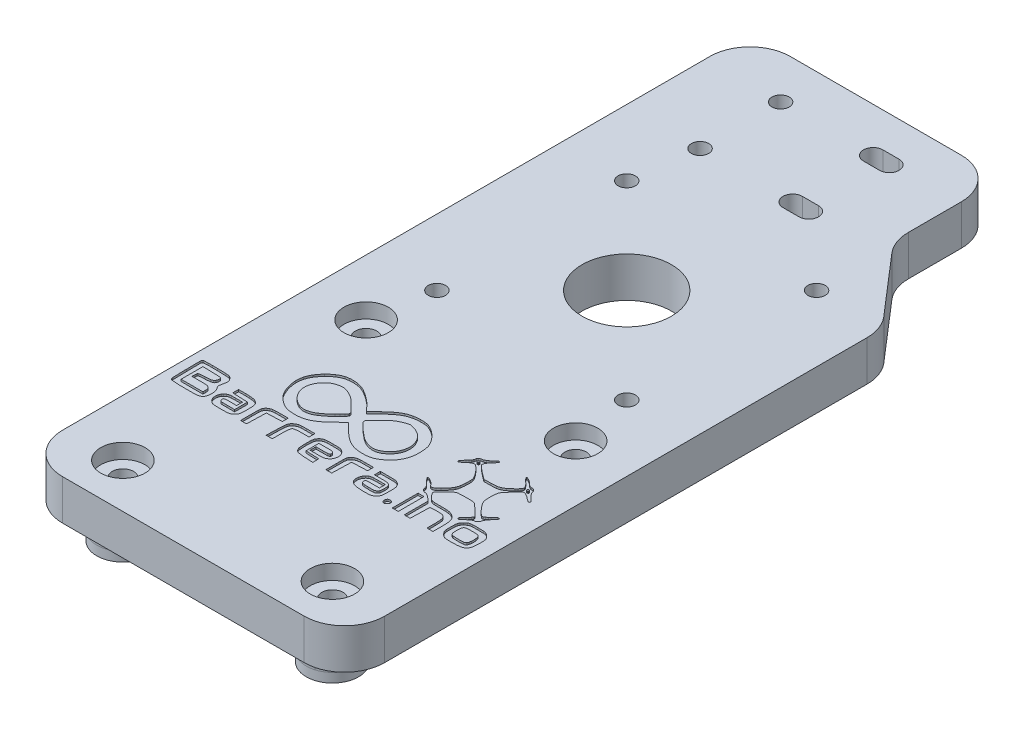
SolidWorks part; units mm, degrees
ref_plane "Alzado" through (0, 0, 0) normal (0, 0, 1) x (1, 0, 0)
ref_plane "Planta" through (0, 0, 0) normal (0, 1, 0) x (1, 0, 0)
ref_plane "Vista lateral" through (0, 0, 0) normal (1, 0, 0) x (0, 0, -1)
sketch "Croquis1" plane through (0, 0, 0) normal (0, 1, 0) x (1, 0, 0)
  line L0 (12.4888, 90.7353) -> (-12.4888, 90.7353)
  line L1 (-12.4888, 90.7353) -> (12.4888, 90.7353)
  line L2 (-40, 39.8326) -> (-40, -80)
  line L3 (-30, -90) -> (30, -90)
  line L4 (40, 39.8326) -> (40, -80)
  line L6 (0, -49) -> (-4.6306, -49) construction
  line L9 (0, 0) -> (0, -51.3503) construction
  line L10 (-12.4888, 90.7353) -> (-30, 90.7353)
  line L11 (24.9172, 61.0325) -> (37.5716, 46.365)
  line L12 (22.4888, 80.7353) -> (22.4888, 67.5648)
  line L13 (-40, 80.7353) -> (-40, 39.8326)
  arc A12 (-40, -80) -> (-30, -90) centre (-30, -80) ccw
  arc A13 (40, -80) -> (30, -90) centre (30, -80) cw
  arc A14 (22.4888, 80.7353) -> (12.4888, 90.7353) centre (12.4888, 80.7353) ccw
  arc A15 (37.5716, 46.365) -> (40, 39.8326) centre (30, 39.8326) cw
  arc A16 (22.4888, 67.5648) -> (24.9172, 61.0325) centre (32.4888, 67.5648) ccw
  arc A17 (-30, 90.7353) -> (-40, 80.7353) centre (-30, 80.7353) ccw
  point P0 (0, 0)
  point P15 (-22.4888, 90.7353)
  point P26 (-40, -90)
  point P29 (40, -90)
  point P40 (22.4888, 90.7353)
  dimension "D1" = 10
  dimension "D3" = 80
extrude "Saliente-Extruir1" add sketch "Croquis1" along normal blind 10 contours L13 L2 L3 L4 L0 region at (-1.4888, 0, 3.0033)
sketch "Croquis2" plane through (0, 0, 0) normal (0, -1, 0) x (1, 0, 0)
  line L0 (-30, 90) -> (30, 90) construction
  line L1 (0, 0) -> (0, 18.1232) construction
  line L2 (-26.0188, 48.8) -> (-13.5394, 48.8) construction
  circle A0 centre (-26.0188, 79) radius 6.5
  circle A1 centre (-26.0188, 79) radius 2.65
  circle A2 centre (-26.0188, 18.6) radius 2.65
  circle A3 centre (-26.0188, 18.6) radius 6.5
  circle A4 centre (26.0188, 79) radius 2.65
  circle A5 centre (26.0188, 79) radius 6.5
  circle A6 centre (26.0188, 18.6) radius 6.5
  circle A7 centre (26.0188, 18.6) radius 2.65
  dimension "D2" = 13
  dimension "D3" = 5.3
  dimension "D1" = 11
  dimension "D4" = 30.2
extrude "Saliente-Extruir2" add sketch "Croquis2" along normal blind 7.3 from surface starting at face at (7.4963, 0, -18.1447)
sketch "Croquis3" plane through (0, 0, 0) normal (0, -1, 0) x (1, 0, 0)
  circle A0 centre (-26.0188, 79) radius 2.65
  circle A1 centre (-26.0188, 18.6) radius 2.65
  circle A2 centre (26.0188, 18.6) radius 2.65
  circle A3 centre (26.0188, 79) radius 2.65
extrude "Cortar-Extruir1" cut sketch "Croquis3" against normal blind 68 and the other way blind 46
sketch "Croquis4" plane through (0, 0, 0) normal (0, -1, 0) x (1, 0, 0)
  line L0 (0, 0) -> (0, -20.1076) construction
  line L1 (0, -20.1076) -> (-7.7372, -20.1076) construction
  circle A0 centre (-23.57, -43.6776) radius 2.15
  circle A1 centre (-23.57, 3.4624) radius 2.15
  circle A2 centre (23.57, 3.4624) radius 2.15
  circle A3 centre (23.57, -43.6776) radius 2.15
  circle A4 centre (0, -20.1076) radius 11.1
  dimension "D1" = 4.3
  dimension "D4" = 22.2
  dimension "D2" = 23.57
  dimension "D3" = 23.57
extrude "Cortar-Extruir2" cut sketch "Croquis4" against normal blind 32 and the other way blind 37
sketch "Croquis6" plane through (0, 10, 0) normal (0, 1, 0) x (1, 0, 0)
  line L0 (1.58, 79.7353) -> (5.58, 79.7353) construction
  line L1 (1.58, 82.1487) -> (5.58, 82.1487)
  line L2 (1.58, 77.322) -> (5.58, 77.322)
  line L3 (1.58, 59.7353) -> (5.58, 59.7353) construction
  line L6 (1.58, 57.322) -> (5.58, 57.322)
  line L9 (0, 0) -> (0, 19.3132) construction
  line L10 (1.58, 62.1487) -> (5.58, 62.1487)
  line L16 (-23.57, 43.6776) -> (-23.57, 65) construction
  line L17 (-24.1067, 69.7353) -> (-27.2294, 69.7353) construction
  circle A15 centre (-21.42, 59.7353) radius 2.15
  circle A16 centre (-21.42, 79.7353) radius 2.15
  circle A17 centre (-21.42, 59.7353) radius 2.15
  circle A18 centre (-21.42, 79.7353) radius 2.15
  arc A19 (1.58, 82.1487) -> (1.58, 77.322) centre (1.58, 79.7353) ccw
  arc A20 (5.58, 77.322) -> (5.58, 82.1487) centre (5.58, 79.7353) ccw
  arc A21 (1.58, 57.322) -> (1.58, 62.1487) centre (1.58, 59.7353) cw
  arc A22 (5.58, 62.1487) -> (5.58, 57.322) centre (5.58, 59.7353) cw
  point P2 (3.58, 79.7353)
  point P9 (3.58, 59.7353)
extrude "Cortar-Extruir3" cut sketch "Croquis6" against normal blind 28 contours A16 | A15 | L6 A22 L10 A21 | L2 A20 L1 A19
fillet "Redondeo4" radius 5 4 edges at (26.0188, 0, 85.5) (-26.0188, 0, 85.5) (26.0188, 0, 25.1) (-26.0188, 0, 25.1)
hole_wizard "Refrentado para tornillo con cabeza troncocónica de M52" positions "Croquis3D1" profile "Croquis10" counterbore size "M5" standard "Ansi Metric" end condition through all
sketch3d "Croquis3D1"
  line L0 (26.0188, -7.3, 18.6) -> (26.0188, 10, 18.6) construction
  line L1 (26.0188, -7.3, 79) -> (26.0188, 10, 79) construction
  line L2 (-26.0188, -7.3, 79) -> (-26.0188, 10, 79) construction
  line L3 (-26.0188, -7.3, 18.6) -> (-26.0188, 10, 18.6) construction
  point P0 (26.0188, 10, 18.6)
  point P4 (26.0188, 10, 79)
  point P8 (-26.0188, 10, 79)
  point P12 (-26.0188, 10, 18.6)
sketch "Croquis10" plane through (26.0188, 10, 18.6) normal (1, 0, 0) x (0, 0, 1)
  line L0 (0, 0) -> (0, 17.3)
  line L1 (0, 17.3) -> (2.65, 17.3)
  line L3 (2.65, 17.3) -> (2.65, 3.7)
  line L4 (2.65, 3.7) -> (5.5, 3.7)
  line L5 (5.5, 3.7) -> (5.5, 0)
  line L7 (5.5, 0) -> (0, 0)
  line L11 (0, -6.35) -> (0, 107.95) construction
  dimension "Diámetro de taladro hasta el siguiente" = 5.3
  dimension "Profundidad de taladro hasta el siguiente" = 17.3
  dimension "Diámetro de refrentado" = 11
  dimension "Profundidad de refrentado" = 3.7
sketch "Croquis11" plane through (0, 10, 0) normal (0, 1, 0) x (1, 0, 0)
  line L0 (21.2059, -36.9748) -> (22.8785, -38.2501)
  line L1 (22.8785, -38.2501) -> (24.6693, -38.2221)
  line L2 (27.7819, -53.7297) -> (27.7819, -55.8067)
  line L3 (27.7819, -55.8067) -> (27.0432, -55.8067)
  line L4 (27.0432, -55.8067) -> (26.3045, -55.8067)
  line L5 (26.3045, -55.8067) -> (26.3045, -53.8368)
  line L6 (23.7692, -50.9322) -> (22.2417, -51.0052)
  line L7 (22.2417, -51.0052) -> (22.1713, -53.4059)
  line L8 (22.1713, -53.4059) -> (22.1008, -55.8067)
  line L9 (22.1008, -55.8067) -> (21.371, -55.8067)
  line L10 (21.371, -55.8067) -> (20.6413, -55.8067)
  line L11 (20.6413, -55.8067) -> (20.6413, -52.8484)
  line L12 (20.6413, -52.8484) -> (20.6413, -49.8902)
  line L13 (20.6413, -49.8902) -> (19.841, -49.1622)
  line L14 (-7.2544, -37.1933) -> (-6.2876, -38.2917)
  line L15 (-6.2876, -38.2917) -> (-4.4504, -36.5228)
  line L16 (-4.41, -44.5781) -> (-6.1939, -42.8294)
  line L17 (-6.1939, -42.8294) -> (-7.9956, -44.5781)
  line L18 (-25.4149, -51.6208) -> (-23.6801, -51.6208)
  line L19 (-23.6801, -51.6208) -> (-23.6801, -52.3594)
  line L20 (-23.6801, -52.3594) -> (-23.6801, -53.0981)
  line L21 (-23.6801, -53.0981) -> (-25.2977, -53.0981)
  line L22 (-24.9113, -54.2062) -> (-23.0645, -54.2062)
  line L23 (-23.0645, -54.2062) -> (-23.0645, -52.6057)
  line L24 (-23.0645, -52.6057) -> (-23.0645, -51.0052)
  line L25 (-23.0645, -51.0052) -> (-24.9728, -50.9333)
  line L26 (-24.9728, -50.9333) -> (-26.8811, -50.8613)
  line L27 (-26.8811, -50.8613) -> (-26.8811, -50.133)
  line L28 (-26.8811, -50.133) -> (-26.8811, -49.4047)
  line L29 (-26.8811, -49.4047) -> (-25.0221, -49.4047)
  line L30 (-14.5696, -50.133) -> (-14.5696, -50.8613)
  line L31 (-14.5696, -50.8613) -> (-16.4779, -50.9333)
  line L32 (-16.4779, -50.9333) -> (-18.3861, -51.0052)
  line L33 (-18.3861, -51.0052) -> (-18.4566, -53.4059)
  line L34 (-18.4566, -53.4059) -> (-18.5271, -55.8067)
  line L35 (-18.5271, -55.8067) -> (-19.2569, -55.8067)
  line L36 (-19.2569, -55.8067) -> (-19.9866, -55.8067)
  line L37 (-19.9866, -55.8067) -> (-19.9866, -53.1159)
  line L38 (-16.6293, -49.4047) -> (-14.5696, -49.4047)
  line L39 (-14.5696, -49.4047) -> (-14.5696, -50.133)
  line L40 (-7.9214, -50.1434) -> (-7.9214, -50.8821)
  line L41 (-7.9214, -50.8821) -> (-9.7189, -50.8821)
  line L42 (-12.1073, -53.6398) -> (-12.1073, -55.8067)
  line L43 (-12.1073, -55.8067) -> (-12.8684, -55.8067)
  line L44 (-12.8684, -55.8067) -> (-13.6295, -55.8067)
  line L45 (-13.6295, -55.8067) -> (-13.5455, -53.1995)
  line L46 (-10.0006, -49.4047) -> (-7.9214, -49.4047)
  line L47 (-7.9214, -49.4047) -> (-7.9214, -50.1434)
  line L48 (-3.1087, -53.5906) -> (-4.9666, -53.5906)
  line L49 (-4.9666, -53.5906) -> (-4.9666, -52.8519)
  line L50 (-4.9666, -52.8519) -> (-4.9666, -52.1132)
  line L51 (-4.9666, -52.1132) -> (-3.2259, -52.1132)
  line L52 (-3.4892, -51.0052) -> (-5.336, -51.0052)
  line L53 (-5.336, -51.0052) -> (-5.336, -52.6057)
  line L54 (-5.336, -52.6057) -> (-5.336, -54.2062)
  line L55 (-5.336, -54.2062) -> (-3.6739, -54.279)
  line L56 (-3.6739, -54.279) -> (-2.0119, -54.3518)
  line L57 (-2.0119, -54.3518) -> (-2.0119, -55.1053)
  line L58 (-2.0119, -55.1053) -> (-2.0119, -55.8588)
  line L59 (-2.0119, -55.8588) -> (-4.0058, -55.7682)
  line L60 (6.6062, -50.133) -> (6.6062, -50.8613)
  line L61 (6.6062, -50.8613) -> (4.6979, -50.9333)
  line L62 (4.6979, -50.9333) -> (2.7896, -51.0052)
  line L63 (2.7896, -51.0052) -> (2.7191, -53.4059)
  line L64 (2.7191, -53.4059) -> (2.6487, -55.8067)
  line L65 (2.6487, -55.8067) -> (1.9189, -55.8067)
  line L66 (1.9189, -55.8067) -> (1.1891, -55.8067)
  line L67 (1.1891, -55.8067) -> (1.1891, -53.1159)
  line L68 (4.5464, -49.4047) -> (6.6062, -49.4047)
  line L69 (6.6062, -49.4047) -> (6.6062, -50.133)
  line L70 (9.9191, -51.6207) -> (11.777, -51.6207)
  line L71 (11.777, -51.6207) -> (11.777, -52.3594)
  line L72 (11.777, -52.3594) -> (11.777, -53.0981)
  line L73 (11.777, -53.0981) -> (10.0363, -53.0981)
  line L74 (10.1678, -50.8821) -> (8.3298, -50.8821)
  line L75 (8.3298, -50.8821) -> (8.3298, -50.1434)
  line L76 (8.3298, -50.1434) -> (8.3298, -49.4047)
  line L77 (8.3298, -49.4047) -> (10.4339, -49.4047)
  line L78 (19.1639, -52.6057) -> (19.1639, -55.8067)
  line L79 (19.1639, -55.8067) -> (18.4252, -55.8067)
  line L80 (18.4252, -55.8067) -> (17.6865, -55.8067)
  line L81 (17.6865, -55.8067) -> (17.6865, -52.6057)
  line L82 (17.6865, -52.6057) -> (17.6865, -49.4047)
  line L83 (17.6865, -49.4047) -> (18.4252, -49.4047)
  line L84 (18.4252, -49.4047) -> (19.1639, -49.4047)
  line L85 (19.1639, -49.4047) -> (19.1639, -52.6057)
  line L86 (-36.2378, -51.6118) -> (-36.2378, -54.3293)
  line L87 (-36.2378, -54.3293) -> (-33.5293, -54.3293)
  line L88 (-33.5293, -54.3293) -> (-30.8207, -54.3293)
  line L89 (-30.8207, -54.3293) -> (-30.8207, -53.6398)
  line L90 (-33.4554, -52.3594) -> (-35.4991, -52.3594)
  line L91 (-35.4991, -52.3594) -> (-35.4991, -51.6485)
  line L92 (-33.8371, -48.9649) -> (-36.2378, -48.8944)
  line L93 (-36.2378, -48.8944) -> (-36.2378, -51.6118)
  arc A0 (21.0913, -32.8038) -> (21.1337, -32.6604) centre (20.8699, -32.6604) ccw
  arc A1 (20.8747, -33.1204) -> (21.0913, -32.8038) centre (14.7218, -28.679) ccw
  arc A2 (20.5897, -33.4901) -> (20.8747, -33.1204) centre (14.8717, -28.7872) ccw
  arc A3 (20.252, -33.8818) -> (20.5897, -33.4901) centre (11.9827, -26.4111) ccw
  arc A4 (20.252, -33.8818) -> (19.9204, -34.2863) centre (24.2894, -37.5294) ccw
  arc A5 (19.9204, -34.2863) -> (19.6532, -34.6947) centre (23.2356, -36.7472) ccw
  arc A6 (19.6532, -34.6947) -> (19.475, -35.0549) centre (22.5197, -36.337) ccw
  arc A7 (19.475, -35.0549) -> (19.4517, -35.2786) centre (19.8316, -35.2051) ccw
  arc A8 (19.4517, -35.2786) -> (19.5678, -35.5077) centre (19.912, -35.1895) ccw
  arc A9 (19.5678, -35.5077) -> (20.0006, -35.9504) centre (27.6789, -28.0096) ccw
  arc A10 (20.0006, -35.9504) -> (20.5593, -36.4556) centre (27.8234, -27.8603) ccw
  arc A11 (20.5593, -36.4556) -> (21.2059, -36.9748) centre (31.2161, -23.8458) ccw
  arc A12 (24.6693, -38.2221) -> (25.9429, -38.1359) centre (24.4776, -25.9378) ccw
  arc A13 (25.9429, -38.1359) -> (26.8036, -37.9023) centre (25.576, -35.0816) ccw
  arc A14 (26.8036, -37.9023) -> (27.6211, -37.4137) centre (25.3173, -34.4872) ccw
  arc A15 (27.6211, -37.4137) -> (28.7871, -36.43) centre (13.704, -19.7348) ccw
  arc A16 (28.7871, -36.43) -> (29.1564, -36.0623) centre (25.1934, -32.4522) ccw
  arc A17 (29.1564, -36.0623) -> (29.4684, -35.6781) centre (25.9297, -33.1229) ccw
  arc A18 (29.4684, -35.6781) -> (29.6907, -35.3289) centre (26.5936, -33.6023) ccw
  arc A19 (29.6907, -35.3289) -> (29.7517, -35.0941) centre (29.2694, -35.0941) ccw
  arc A20 (29.7517, -35.0941) -> (29.6898, -34.8583) centre (29.2722, -35.0941) ccw
  arc A21 (29.6898, -34.8583) -> (29.4624, -34.5047) centre (26.5, -36.6592) ccw
  arc A22 (29.4624, -34.5047) -> (29.1439, -34.1146) centre (25.823, -37.1515) ccw
  arc A23 (29.1439, -34.1146) -> (28.7668, -33.7398) centre (25.0263, -37.8801) ccw
  arc A24 (28.3895, -33.3826) -> (28.7668, -33.7398) centre (36.2482, -25.4589) ccw
  arc A25 (28.0712, -33.0456) -> (28.3895, -33.3826) centre (33.3803, -28.3505) ccw
  arc A26 (27.8271, -32.7551) -> (28.0712, -33.0456) centre (33.7145, -28.0549) ccw
  arc A27 (27.7819, -32.6261) -> (27.8271, -32.7551) centre (27.9887, -32.6261) ccw
  arc A28 (27.9314, -32.5219) -> (27.7819, -32.6261) centre (27.893, -32.6261) ccw
  arc A29 (28.4829, -32.7723) -> (27.9314, -32.5219) centre (26.4963, -36.415) ccw
  arc A30 (29.1144, -33.1755) -> (28.4829, -32.7723) centre (25.8799, -37.5452) ccw
  arc A31 (29.6058, -33.6208) -> (29.1144, -33.1755) centre (27.1189, -35.8714) ccw
  arc A32 (29.6058, -33.6208) -> (29.8241, -33.8189) centre (30.7207, -32.6118) ccw
  arc A33 (29.8241, -33.8189) -> (30.0918, -33.9864) centre (31.0036, -32.231) ccw
  arc A34 (30.0918, -33.9864) -> (30.3662, -34.1011) centre (30.9194, -32.393) ccw
  arc A35 (30.3662, -34.1011) -> (30.6025, -34.1384) centre (30.6025, -33.3717) ccw
  arc A36 (31.0273, -34.2107) -> (30.6025, -34.1384) centre (30.6025, -35.4228) ccw
  arc A37 (31.3908, -34.4189) -> (31.0273, -34.2107) centre (30.6468, -35.2964) ccw
  arc A38 (31.6351, -34.7275) -> (31.3908, -34.4189) centre (30.7432, -35.1826) ccw
  arc A39 (31.7216, -35.0873) -> (31.6351, -34.7275) centre (30.93, -35.0873) ccw
  arc A40 (31.7216, -35.0873) -> (31.7798, -35.2814) centre (32.0742, -35.0873) ccw
  arc A41 (31.7798, -35.2814) -> (32.029, -35.6279) centre (36.19, -32.373) ccw
  arc A42 (32.029, -35.6279) -> (32.3673, -36.0237) centre (36.7426, -31.9408) ccw
  arc A43 (32.3673, -36.0237) -> (32.7681, -36.4251) centre (38.5208, -30.2813) ccw
  arc A44 (33.5247, -37.2065) -> (32.7681, -36.4251) centre (25.1623, -44.5478) ccw
  arc A45 (33.4972, -37.5237) -> (33.5247, -37.2065) centre (33.3591, -37.3519) ccw
  arc A46 (33.1213, -37.5406) -> (33.4972, -37.5237) centre (33.2977, -37.2755) ccw
  arc A47 (32.2103, -36.8736) -> (33.1213, -37.5406) centre (40.0855, -27.0739) ccw
  arc A48 (32.2103, -36.8736) -> (31.8107, -36.5806) centre (28.7118, -41.2269) ccw
  arc A49 (31.8107, -36.5806) -> (31.3976, -36.3331) centre (29.0438, -40.7291) ccw
  arc A50 (31.3976, -36.3331) -> (31.0263, -36.1571) centre (29.4233, -40.0205) ccw
  arc A51 (31.0263, -36.1571) -> (30.781, -36.1083) centre (30.781, -36.7482) ccw
  arc A52 (30.781, -36.1083) -> (30.3896, -36.2526) centre (30.781, -36.7112) ccw
  arc A53 (30.3896, -36.2526) -> (29.7061, -36.8888) centre (37.4183, -44.4886) ccw
  arc A54 (29.7061, -36.8888) -> (28.8527, -37.8286) centre (40.7849, -47.8061) ccw
  arc A55 (28.8527, -37.8286) -> (27.8137, -39.1195) centre (62.8856, -66.2863) ccw
  arc A56 (27.8137, -39.1195) -> (27.6752, -39.3998) centre (28.4349, -39.6007) ccw
  arc A57 (27.6752, -39.3998) -> (27.5725, -39.8921) centre (32.2747, -40.6163) ccw
  arc A58 (27.5725, -39.8921) -> (27.5056, -40.5213) centre (34.2365, -40.9184) ccw
  arc A59 (27.5056, -40.5213) -> (27.4838, -41.2612) centre (40.0467, -41.2611) ccw
  arc A60 (27.4838, -41.2612) -> (27.5091, -42.1737) centre (43.9681, -41.2612) ccw
  arc A61 (27.5091, -42.1737) -> (27.5946, -42.7976) centre (31.409, -41.9574) ccw
  arc A62 (27.5946, -42.7976) -> (27.7618, -43.297) centre (30.0184, -42.2637) ccw
  arc A63 (27.7618, -43.297) -> (28.0408, -43.7901) centre (30.7743, -41.9176) ccw
  arc A64 (28.0408, -43.7901) -> (28.7456, -44.7191) centre (37.9818, -36.9802) ccw
  arc A65 (28.7456, -44.7191) -> (29.5519, -45.5973) centre (38.834, -36.2662) ccw
  arc A66 (29.5519, -45.5973) -> (30.3126, -46.3009) centre (39.5998, -35.4963) ccw
  arc A67 (30.3126, -46.3009) -> (30.7147, -46.4499) centre (30.7147, -45.8331) ccw
  arc A68 (30.7147, -46.4499) -> (30.9123, -46.3976) centre (30.7147, -46.0506) ccw
  arc A69 (30.9123, -46.3976) -> (31.2441, -46.1885) centre (28.7324, -42.5703) ccw
  arc A70 (31.2441, -46.1885) -> (31.6205, -45.9008) centre (28.3019, -41.9503) ccw
  arc A71 (31.6205, -45.9008) -> (31.9965, -45.5601) centre (27.2572, -40.7067) ccw
  arc A72 (32.8477, -44.7974) -> (31.9965, -45.5601) centre (41.3205, -55.1088) ccw
  arc A73 (33.2215, -44.7747) -> (32.8477, -44.7974) centre (33.0502, -45.0439) ccw
  arc A74 (33.2775, -45.0802) -> (33.2215, -44.7747) centre (33.1077, -44.9535) ccw
  arc A75 (32.5784, -45.9305) -> (33.2775, -45.0802) centre (23.8185, -38.0164) ccw
  arc A76 (32.5784, -45.9305) -> (32.2116, -46.3699) centre (38.0114, -50.8389) ccw
  arc A77 (32.2116, -46.3699) -> (31.8959, -46.8194) centre (37.1328, -50.1619) ccw
  arc A78 (31.8959, -46.8194) -> (31.6637, -47.2213) centre (36.3389, -49.6552) ccw
  arc A79 (31.6637, -47.2213) -> (31.5908, -47.478) centre (32.2502, -47.5266) ccw
  arc A80 (31.4892, -47.8386) -> (31.5908, -47.478) centre (30.6547, -47.409) ccw
  arc A81 (31.2531, -48.1407) -> (31.4892, -47.8386) centre (30.5769, -47.369) ccw
  arc A82 (30.9146, -48.3427) -> (31.2531, -48.1407) centre (30.5339, -47.3199) ccw
  arc A83 (30.5203, -48.416) -> (30.9146, -48.3427) centre (30.5073, -47.2486) ccw
  arc A84 (30.5203, -48.416) -> (30.3325, -48.4675) centre (30.5245, -48.7998) ccw
  arc A85 (30.3325, -48.4675) -> (29.9866, -48.6842) centre (33.1974, -53.4243) ccw
  arc A86 (29.9866, -48.6842) -> (29.5881, -48.9774) centre (33.5513, -53.9467) ccw
  arc A87 (29.5881, -48.9774) -> (29.1801, -49.3238) centre (35.0172, -55.7848) ccw
  arc A88 (28.364, -49.9885) -> (29.1801, -49.3238) centre (22.286, -41.6929) ccw
  arc A89 (28.0754, -49.9194) -> (28.364, -49.9885) centre (28.249, -49.8316) ccw
  arc A90 (28.1178, -49.5284) -> (28.0754, -49.9194) centre (28.3976, -49.7565) ccw
  arc A91 (28.8619, -48.6947) -> (28.1178, -49.5284) centre (37.7922, -57.4149) ccw
  arc A92 (28.8619, -48.6947) -> (29.2027, -48.3259) centre (22.3349, -42.3212) ccw
  arc A93 (29.2027, -48.3259) -> (29.4904, -47.9715) centre (24.5081, -44.2213) ccw
  arc A94 (29.4904, -47.9715) -> (29.7059, -47.6656) centre (24.7454, -44.3999) ccw
  arc A95 (29.7059, -47.6656) -> (29.7517, -47.5125) centre (29.4734, -47.5125) ccw
  arc A96 (29.7517, -47.5125) -> (29.6099, -47.1734) centre (29.2756, -47.5125) ccw
  arc A97 (29.6099, -47.1734) -> (28.2818, -45.8863) centre (-46.5175, -124.3919) ccw
  arc A98 (28.2818, -45.8863) -> (26.9479, -44.641) centre (-33.4747, -110.7029) ccw
  arc A99 (26.9479, -44.641) -> (26.5367, -44.4493) centre (26.4373, -45.1992) ccw
  arc A100 (26.5367, -44.4493) -> (25.5251, -44.3732) centre (25.3606, -53.3222) ccw
  arc A101 (25.5251, -44.3732) -> (24.1194, -44.3783) centre (24.9372, -76.3487) ccw
  arc A102 (24.1194, -44.3783) -> (22.7363, -44.4336) centre (25.3478, -92.4017) ccw
  arc A103 (22.7363, -44.4336) -> (22.257, -44.5588) centre (22.8037, -45.6717) ccw
  arc A104 (22.257, -44.5588) -> (21.5388, -45.0352) centre (23.7328, -47.5631) ccw
  arc A105 (21.5388, -45.0352) -> (20.5307, -45.9728) centre (34.6641, -60.1582) ccw
  arc A106 (20.5307, -45.9728) -> (19.5754, -46.9698) centre (41.5808, -67.1003) ccw
  arc A107 (19.5754, -46.9698) -> (19.4101, -47.3953) centre (20.0405, -47.3953) ccw
  arc A108 (19.4101, -47.3953) -> (19.4589, -47.5949) centre (19.8432, -47.3953) ccw
  arc A109 (19.4589, -47.5949) -> (19.6413, -47.906) centre (22.5899, -45.9681) ccw
  arc A110 (19.6413, -47.906) -> (19.8958, -48.2536) centre (23.1921, -45.5724) ccw
  arc A111 (19.8958, -48.2536) -> (20.1971, -48.5927) centre (23.946, -44.9591) ccw
  arc A112 (20.1971, -48.5927) -> (20.7406, -49.0822) centre (24.0717, -44.8373) ccw
  arc A113 (20.7406, -49.0822) -> (21.1836, -49.3013) centre (21.4864, -48.1318) ccw
  arc A114 (21.1836, -49.3013) -> (21.8069, -49.3879) centre (21.869, -46.6541) ccw
  arc A115 (21.8069, -49.3879) -> (23.3365, -49.4056) centre (23.3633, 19.1327) ccw
  arc A116 (24.5942, -49.427) -> (23.3365, -49.4056) centre (23.3217, -87.2988) ccw
  arc A117 (25.3883, -49.502) -> (24.5942, -49.427) centre (24.3728, -56.0141) ccw
  arc A118 (25.9719, -49.6493) -> (25.3883, -49.502) centre (24.8872, -52.7154) ccw
  arc A119 (26.4953, -49.8982) -> (25.9719, -49.6493) centre (25.0386, -52.2874) ccw
  arc A120 (27.1483, -50.4461) -> (26.4953, -49.8982) centre (25.0168, -52.3232) ccw
  arc A121 (27.535, -51.1168) -> (27.1483, -50.4461) centre (25.6789, -51.7401) ccw
  arc A122 (27.7286, -52.0988) -> (27.535, -51.1168) centre (23.8558, -52.3523) ccw
  arc A123 (27.7819, -53.7297) -> (27.7286, -52.0988) centre (2.8088, -53.7297) ccw
  arc A124 (26.3045, -53.8368) -> (26.2132, -52.1726) centre (11.0959, -53.8368) ccw
  arc A125 (26.2132, -52.1726) -> (25.8585, -51.3646) centre (24.7481, -52.3339) ccw
  arc A126 (25.8585, -51.3646) -> (25.1454, -50.9852) centre (25.0043, -52.1102) ccw
  arc A127 (25.1454, -50.9852) -> (23.7692, -50.9322) centre (24.1509, -58.917) ccw
  arc A128 (19.841, -49.1622) -> (19.4975, -48.883) centre (17.165, -52.1038) ccw
  arc A129 (19.4975, -48.883) -> (19.1276, -48.6459) centre (17.2302, -52.0137) ccw
  arc A130 (19.1276, -48.6459) -> (18.784, -48.4784) centre (17.5449, -51.4552) ccw
  arc A131 (18.784, -48.4784) -> (18.536, -48.427) centre (18.5264, -49.0973) ccw
  arc A132 (18.1087, -48.3454) -> (18.536, -48.427) centre (18.5539, -47.1732) ccw
  arc A133 (17.7548, -48.1239) -> (18.1087, -48.3454) centre (18.4886, -47.3452) ccw
  arc A134 (17.5223, -47.7919) -> (17.7548, -48.1239) centre (18.4408, -47.3959) ccw
  arc A135 (17.4403, -47.3945) -> (17.5223, -47.7919) centre (18.4441, -47.3945) ccw
  arc A136 (17.4403, -47.3945) -> (17.3775, -47.1674) centre (16.9977, -47.3945) ccw
  arc A137 (17.3775, -47.1674) -> (17.1333, -46.8014) centre (13.5687, -49.445) ccw
  arc A138 (17.1333, -46.8014) -> (16.7953, -46.3905) centre (12.8661, -49.966) ccw
  arc A139 (16.7953, -46.3905) -> (16.3953, -45.9854) centre (11.6494, -51.0733) ccw
  arc A140 (16.0069, -45.5994) -> (16.3953, -45.9854) centre (22.2923, -39.6634) ccw
  arc A141 (15.7072, -45.247) -> (16.0069, -45.5994) centre (19.2292, -42.5563) ccw
  arc A142 (15.5071, -44.9568) -> (15.7072, -45.247) centre (18.5974, -43.039) ccw
  arc A143 (15.5205, -44.8404) -> (15.5071, -44.9568) centre (15.5872, -44.9071) ccw
  arc A144 (15.8056, -44.7937) -> (15.5205, -44.8404) centre (15.6956, -45.0154) ccw
  arc A145 (16.5413, -45.2028) -> (15.8056, -44.7937) centre (11.8213, -52.8247) ccw
  arc A146 (17.2434, -45.6947) -> (16.5413, -45.2028) centre (12.5557, -51.6387) ccw
  arc A147 (17.5312, -46.0856) -> (17.2434, -45.6947) centre (16.6764, -46.4136) ccw
  arc A148 (17.5312, -46.0856) -> (17.8107, -46.3755) centre (18.0132, -45.9006) ccw
  arc A149 (17.8107, -46.3755) -> (18.2372, -46.4008) centre (18.0594, -45.7922) ccw
  arc A150 (18.2372, -46.4008) -> (18.8001, -46.1125) centre (17.7654, -44.7859) ccw
  arc A151 (18.8001, -46.1125) -> (19.4446, -45.5266) centre (15.2479, -41.558) ccw
  arc A152 (19.4446, -45.5266) -> (20.5035, -44.3215) centre (3.4958, -30.445) ccw
  arc A153 (20.5035, -44.3215) -> (21.0627, -43.4335) centre (17.171, -41.6026) ccw
  arc A154 (21.0627, -43.4335) -> (21.347, -42.5085) centre (17.9604, -41.974) ccw
  arc A155 (21.347, -42.5085) -> (21.4703, -41.2209) centre (10.8773, -40.8561) ccw
  arc A156 (21.4703, -41.2209) -> (21.482, -40.2024) centre (-0.6913, -40.4577) ccw
  arc A157 (21.482, -40.2024) -> (21.4164, -39.5926) centre (18.2696, -40.2394) ccw
  arc A158 (21.4164, -39.5926) -> (21.248, -39.1085) centre (19.5099, -39.9845) ccw
  arc A159 (21.248, -39.1085) -> (20.9256, -38.5706) centre (17.4156, -41.04) ccw
  arc A160 (20.9256, -38.5706) -> (20.1711, -37.5811) centre (7.6597, -47.9035) ccw
  arc A161 (20.1711, -37.5811) -> (19.44, -36.7952) centre (13.2086, -43.3255) ccw
  arc A162 (19.44, -36.7952) -> (18.7936, -36.2546) centre (14.9961, -41.4522) ccw
  arc A163 (18.7936, -36.2546) -> (18.3452, -36.1083) centre (18.3452, -36.8684) ccw
  arc A164 (18.3452, -36.1083) -> (18.0984, -36.1647) centre (18.3452, -36.676) ccw
  arc A165 (18.0984, -36.1647) -> (17.7151, -36.3738) centre (20.0008, -40.107) ccw
  arc A166 (17.7151, -36.3738) -> (17.2866, -36.6663) centre (20.4553, -40.8493) ccw
  arc A167 (17.2866, -36.6663) -> (16.8686, -37.0123) centre (21.0795, -41.6733) ccw
  arc A168 (16.0525, -37.677) -> (16.8686, -37.0123) centre (9.9745, -29.3814) ccw
  arc A169 (15.764, -37.6079) -> (16.0525, -37.677) centre (15.9375, -37.5201) ccw
  arc A170 (15.8063, -37.2169) -> (15.764, -37.6079) centre (16.0861, -37.445) ccw
  arc A171 (16.5504, -36.3832) -> (15.8063, -37.2169) centre (25.4807, -45.1034) ccw
  arc A172 (16.5504, -36.3832) -> (16.8911, -36.0071) centre (11.7059, -31.6527) ccw
  arc A173 (16.8911, -36.0071) -> (17.1789, -35.6306) centre (12.9444, -32.6927) ccw
  arc A174 (17.1789, -35.6306) -> (17.3879, -35.2986) centre (13.5656, -33.1237) ccw
  arc A175 (17.3879, -35.2986) -> (17.4403, -35.1007) centre (17.04, -35.1007) ccw
  arc A176 (17.5236, -34.7409) -> (17.4403, -35.1007) centre (18.2582, -35.1007) ccw
  arc A177 (17.7601, -34.4272) -> (17.5236, -34.7409) centre (18.4551, -35.1971) ccw
  arc A178 (18.1075, -34.2131) -> (17.7601, -34.4272) centre (18.5153, -35.2637) ccw
  arc A179 (18.5061, -34.1384) -> (18.1075, -34.2131) centre (18.5061, -35.2401) ccw
  arc A180 (18.5061, -34.1384) -> (18.7502, -34.084) centre (18.5061, -33.5645) ccw
  arc A181 (18.7502, -34.084) -> (19.1218, -33.8853) centre (17.017, -30.3957) ccw
  arc A182 (19.1218, -33.8853) -> (19.5349, -33.6065) centre (16.5887, -29.6855) ccw
  arc A183 (19.5349, -33.6065) -> (19.935, -33.2766) centre (16.085, -29.0151) ccw
  arc A184 (20.6032, -32.6873) -> (19.935, -33.2766) centre (44.8837, -60.8919) ccw
  arc A185 (20.9136, -32.4782) -> (20.6032, -32.6873) centre (21.6407, -33.8926) ccw
  arc A186 (21.0621, -32.498) -> (20.9136, -32.4782) centre (20.9736, -32.595) ccw
  arc A187 (21.1337, -32.6604) -> (21.0621, -32.498) centre (20.9139, -32.6604) ccw
  arc A188 (-11.2066, -34.0972) -> (-12.4237, -33.55) centre (-14.6005, -40.019) ccw
  arc A189 (-9.758, -35.0199) -> (-11.2066, -34.0972) centre (-20.3414, -50.0361) ccw
  arc A190 (-8.3526, -36.1115) -> (-9.758, -35.0199) centre (-20.8047, -50.6934) ccw
  arc A191 (-7.2544, -37.1933) -> (-8.3526, -36.1115) centre (-15.3965, -44.3602) ccw
  arc A192 (-2.6655, -34.9705) -> (-4.4504, -36.5228) centre (11.7706, -53.3708) ccw
  arc A193 (-1.1038, -33.9907) -> (-2.6655, -34.9705) centre (2.7659, -41.8934) ccw
  arc A194 (0.4457, -33.4577) -> (-1.1038, -33.9907) centre (1.8084, -39.9381) ccw
  arc A195 (2.174, -33.2791) -> (0.4457, -33.4577) centre (2.163, -41.6241) ccw
  arc A196 (3.222, -33.3102) -> (2.174, -33.2791) centre (2.1495, -51.7899) ccw
  arc A197 (3.9297, -33.4121) -> (3.222, -33.3102) centre (2.9782, -37.5109) ccw
  arc A198 (4.5659, -33.6252) -> (3.9297, -33.4121) centre (3.1311, -36.852) ccw
  arc A199 (5.3559, -34.0178) -> (4.5659, -33.6252) centre (0.3748, -43.051) ccw
  arc A200 (6.4374, -34.7633) -> (5.3559, -34.0178) centre (2.1661, -39.8024) ccw
  arc A201 (7.472, -35.781) -> (6.4374, -34.7633) centre (0.0985, -42.2418) ccw
  arc A202 (8.3249, -36.9161) -> (7.472, -35.781) centre (0.3596, -42.013) ccw
  arc A203 (8.8566, -38.013) -> (8.3249, -36.9161) centre (3.9586, -39.7101) ccw
  arc A204 (8.9808, -38.4867) -> (8.8566, -38.013) centre (5.8564, -39.0525) ccw
  arc A205 (9.0855, -39.174) -> (8.9808, -38.4867) centre (-3.2302, -40.6982) ccw
  arc A206 (9.1585, -39.9357) -> (9.0855, -39.174) centre (-4.6803, -40.8777) ccw
  arc A207 (9.1847, -40.6635) -> (9.1585, -39.9357) centre (-2.2042, -40.7091) ccw
  arc A208 (8.9225, -42.6991) -> (9.1847, -40.6635) centre (1.3942, -40.6947) ccw
  arc A209 (8.1386, -44.5008) -> (8.9225, -42.6991) centre (2.5763, -41.0094) ccw
  arc A210 (6.8383, -46.0221) -> (8.1386, -44.5008) centre (2.3408, -40.8616) ccw
  arc A211 (5.0604, -47.2341) -> (6.8383, -46.0221) centre (0.8605, -39.1631) ccw
  arc A212 (4.4601, -47.4953) -> (5.0604, -47.2341) centre (2.8797, -43.0435) ccw
  arc A213 (3.8478, -47.6615) -> (4.4601, -47.4953) centre (3.0645, -43.564) ccw
  arc A214 (3.1254, -47.7531) -> (3.8478, -47.6615) centre (2.7593, -41.9675) ccw
  arc A215 (2.174, -47.7859) -> (3.1254, -47.7531) centre (2.0769, -31.1828) ccw
  arc A216 (0.4338, -47.6148) -> (2.174, -47.7859) centre (2.1247, -39.3523) ccw
  arc A217 (-1.118, -47.0874) -> (0.4338, -47.6148) centre (1.7437, -41.2137) ccw
  arc A218 (-2.6656, -46.1147) -> (-1.118, -47.0874) centre (2.604, -39.448) ccw
  arc A219 (-4.41, -44.5781) -> (-2.6656, -46.1147) centre (10.8696, -28.991) ccw
  arc A220 (-9.7502, -46.1126) -> (-7.9956, -44.5781) centre (-23.6477, -28.452) ccw
  arc A221 (-11.2973, -47.0843) -> (-9.7502, -46.1126) centre (-15.0932, -39.3229) ccw
  arc A222 (-12.8415, -47.6144) -> (-11.2973, -47.0843) centre (-14.1926, -41.1643) ccw
  arc A223 (-14.5696, -47.7932) -> (-12.8415, -47.6144) centre (-14.5675, -39.3742) ccw
  arc A224 (-15.9709, -47.6944) -> (-14.5696, -47.7932) centre (-14.5672, -37.7769) ccw
  arc A225 (-17.1223, -47.394) -> (-15.9709, -47.6944) centre (-15.2413, -42.54) ccw
  arc A226 (-18.1941, -46.834) -> (-17.1223, -47.394) centre (-15.1651, -42.3431) ccw
  arc A227 (-19.3543, -45.9391) -> (-18.1941, -46.834) centre (-11.7451, -37.2726) ccw
  arc A228 (-20.509, -44.5167) -> (-19.3543, -45.9391) centre (-15.7483, -41.832) ccw
  arc A229 (-21.3221, -42.5894) -> (-20.509, -44.5167) centre (-12.5182, -40.0105) ccw
  arc A230 (-21.6809, -40.5149) -> (-21.3221, -42.5894) centre (-12.4161, -39.9806) ccw
  arc A231 (-21.4881, -38.655) -> (-21.6809, -40.5149) centre (-15.8553, -40.1789) ccw
  arc A232 (-20.7747, -37.0166) -> (-21.4881, -38.655) centre (-15.5774, -40.2541) ccw
  arc A233 (-19.5438, -35.4365) -> (-20.7747, -37.0166) centre (-12.6383, -42.0849) ccw
  arc A234 (-18.0237, -34.1586) -> (-19.5438, -35.4365) centre (-12.7418, -41.9852) ccw
  arc A235 (-16.4496, -33.4217) -> (-18.0237, -34.1586) centre (-14.8904, -38.8015) ccw
  arc A236 (-15.4975, -33.2326) -> (-16.4496, -33.4217) centre (-14.8782, -38.8437) ccw
  arc A237 (-14.4621, -33.1922) -> (-15.4975, -33.2326) centre (-14.6951, -40.5026) ccw
  arc A238 (-13.4141, -33.2991) -> (-14.4621, -33.1922) centre (-14.7026, -40.7379) ccw
  arc A239 (-12.4237, -33.55) -> (-13.4141, -33.2991) centre (-14.5544, -39.8819) ccw
  arc A240 (-29.9868, -48.6415) -> (-30.2498, -48.2283) centre (-32.9056, -50.2093) ccw
  arc A241 (-29.878, -48.9816) -> (-29.9868, -48.6415) centre (-30.8497, -49.105) ccw
  arc A242 (-29.8848, -49.3878) -> (-29.878, -48.9816) centre (-31.2919, -49.1611) ccw
  arc A243 (-30.0166, -50.0647) -> (-29.8848, -49.3878) centre (-40.3176, -47.7075) ccw
  arc A244 (-30.0166, -50.0647) -> (-30.1478, -50.7337) centre (-19.3945, -52.4954) ccw
  arc A245 (-30.1478, -50.7337) -> (-30.1573, -51.1335) centre (-28.719, -50.9678) ccw
  arc A246 (-30.1573, -51.1335) -> (-30.056, -51.4574) centre (-29.2579, -51.0299) ccw
  arc A247 (-30.056, -51.4574) -> (-29.8134, -51.8283) centre (-27.8166, -50.2576) ccw
  arc A248 (-29.4446, -52.5937) -> (-29.8134, -51.8283) centre (-31.3603, -53.0451) ccw
  arc A249 (-29.327, -53.6346) -> (-29.4446, -52.5937) centre (-33.7412, -53.6062) ccw
  arc A250 (-29.4563, -54.6461) -> (-29.327, -53.6346) centre (-33.5622, -53.6074) ccw
  arc A251 (-29.8358, -55.3142) -> (-29.4563, -54.6461) centre (-30.8587, -54.2913) ccw
  arc A252 (-30.2437, -55.5836) -> (-29.8358, -55.3142) centre (-30.699, -54.4511) ccw
  arc A253 (-30.7967, -55.7273) -> (-30.2437, -55.5836) centre (-31.0775, -53.5095) ccw
  arc A254 (-31.7248, -55.7924) -> (-30.7967, -55.7273) centre (-31.8435, -47.4578) ccw
  arc A255 (-33.7263, -55.8067) -> (-31.7248, -55.7924) centre (-33.7262, 84.673) ccw
  arc A256 (-35.2701, -55.79) -> (-33.7263, -55.8067) centre (-33.7262, 15.701) ccw
  arc A257 (-36.3655, -55.7344) -> (-35.2701, -55.79) centre (-34.8634, -36.9587) ccw
  arc A258 (-37.1431, -55.649) -> (-36.3655, -55.7344) centre (-35.3102, -42.5441) ccw
  arc A259 (-37.4197, -55.5112) -> (-37.1431, -55.649) centre (-37.0757, -55.1672) ccw
  arc A260 (-37.6465, -54.984) -> (-37.4197, -55.5112) centre (-36.8716, -54.963) ccw
  arc A261 (-37.7201, -51.548) -> (-37.6465, -54.984) centre (264.888, -46.7835) ccw
  arc A262 (-37.7553, -48.105) -> (-37.7201, -51.548) centre (274.3577, -46.6341) ccw
  arc A263 (-37.5444, -47.5924) -> (-37.7553, -48.105) centre (-37.0352, -48.1016) ccw
  arc A264 (-37.3918, -47.5254) -> (-37.5444, -47.5924) centre (-37.3822, -47.7545) ccw
  arc A265 (-36.4509, -47.4918) -> (-37.3918, -47.5254) centre (-34.2358, -122.6856) ccw
  arc A266 (-35.3434, -47.476) -> (-36.4509, -47.4918) centre (-35.3773, -83.9363) ccw
  arc A267 (-34.0617, -47.4898) -> (-35.3434, -47.476) centre (-35.4039, -112.6744) ccw
  arc A268 (-31.8943, -47.5471) -> (-34.0617, -47.4898) centre (-37.8818, -233.0185) ccw
  arc A269 (-31.1101, -47.6351) -> (-31.8943, -47.5471) centre (-32.0545, -52.5092) ccw
  arc A270 (-30.6515, -47.8332) -> (-31.1101, -47.6351) centre (-31.3314, -48.7771) ccw
  arc A271 (-30.2498, -48.2283) -> (-30.6515, -47.8332) centre (-31.7329, -49.3346) ccw
  arc A272 (-21.9216, -50.1493) -> (-22.4665, -49.7649) centre (-23.5877, -51.933) ccw
  arc A273 (-21.6287, -50.605) -> (-21.9216, -50.1493) centre (-22.6741, -50.9549) ccw
  arc A274 (-21.4956, -51.3219) -> (-21.6287, -50.605) centre (-24.115, -51.4372) ccw
  arc A275 (-21.464, -52.7601) -> (-21.4956, -51.3219) centre (-54.1764, -52.7601) ccw
  arc A276 (-21.4846, -53.815) -> (-21.464, -52.7601) centre (-48.5023, -52.7601) ccw
  arc A277 (-21.5661, -54.3896) -> (-21.4846, -53.815) centre (-24.3384, -53.7035) ccw
  arc A278 (-21.7429, -54.799) -> (-21.5661, -54.3896) centre (-22.8827, -54.0638) ccw
  arc A279 (-22.0684, -55.2023) -> (-21.7429, -54.799) centre (-23.7957, -53.475) ccw
  arc A280 (-22.491, -55.5364) -> (-22.0684, -55.2023) centre (-23.7079, -53.5628) ccw
  arc A281 (-22.9291, -55.7119) -> (-22.491, -55.5364) centre (-23.2166, -54.3596) ccw
  arc A282 (-23.5789, -55.7889) -> (-22.9291, -55.7119) centre (-23.6743, -52.2067) ccw
  arc A283 (-24.9112, -55.8067) -> (-23.5789, -55.7889) centre (-24.9112, -5.743) ccw
  arc A284 (-26.2435, -55.7889) -> (-24.9112, -55.8067) centre (-24.9113, -5.743) ccw
  arc A285 (-26.8934, -55.7119) -> (-26.2435, -55.7889) centre (-26.1482, -52.2067) ccw
  arc A286 (-27.3314, -55.5364) -> (-26.8934, -55.7119) centre (-26.6059, -54.3596) ccw
  arc A287 (-27.7541, -55.2023) -> (-27.3314, -55.5364) centre (-26.1146, -53.5628) ccw
  arc A288 (-28.0249, -54.8778) -> (-27.7541, -55.2023) centre (-26.0887, -53.5369) ccw
  arc A289 (-28.2127, -54.5304) -> (-28.0249, -54.8778) centre (-26.5464, -53.8539) ccw
  arc A290 (-28.3219, -54.1467) -> (-28.2127, -54.5304) centre (-26.5072, -53.838) ccw
  arc A291 (-28.3584, -53.7137) -> (-28.3219, -54.1467) centre (-25.7769, -53.7137) ccw
  arc A292 (-28.3219, -53.2807) -> (-28.3584, -53.7137) centre (-25.7769, -53.7137) ccw
  arc A293 (-28.2127, -52.897) -> (-28.3219, -53.2807) centre (-26.5072, -53.5894) ccw
  arc A294 (-28.0249, -52.5497) -> (-28.2127, -52.897) centre (-26.5464, -53.5735) ccw
  arc A295 (-27.7541, -52.2251) -> (-28.0249, -52.5497) centre (-26.0887, -53.8905) ccw
  arc A296 (-27.3564, -51.9025) -> (-27.7541, -52.2251) centre (-26.0068, -53.9724) ccw
  arc A297 (-26.9543, -51.7252) -> (-27.3564, -51.9025) centre (-26.6145, -53.0403) ccw
  arc A298 (-26.3993, -51.6423) -> (-26.9543, -51.7252) centre (-26.2818, -54.3283) ccw
  arc A299 (-25.4149, -51.6208) -> (-26.3993, -51.6423) centre (-25.4149, -74.1297) ccw
  arc A300 (-25.2977, -53.0981) -> (-26.3095, -53.1102) centre (-25.2977, -95.637) ccw
  arc A301 (-26.3095, -53.1102) -> (-26.6715, -53.1778) centre (-26.2822, -54.2591) ccw
  arc A302 (-26.6715, -53.1778) -> (-26.8195, -53.3406) centre (-26.5919, -53.3989) ccw
  arc A303 (-26.8195, -53.3406) -> (-26.8366, -53.6521) centre (-26.0433, -53.5395) ccw
  arc A304 (-26.8366, -53.6521) -> (-26.7194, -53.959) centre (-26.1044, -53.5482) ccw
  arc A305 (-26.7194, -53.959) -> (-26.4942, -54.1235) centre (-26.382, -53.7336) ccw
  arc A306 (-26.4942, -54.1235) -> (-26.0426, -54.1927) centre (-26, -52.4061) ccw
  arc A307 (-26.0426, -54.1927) -> (-24.9113, -54.2062) centre (-24.9113, -6.6972) ccw
  arc A308 (-24.2037, -49.4286) -> (-25.0221, -49.4047) centre (-25.0221, -63.4019) ccw
  arc A309 (-23.4747, -49.5012) -> (-24.2037, -49.4286) centre (-24.7292, -58.401) ccw
  arc A310 (-22.8738, -49.6142) -> (-23.4747, -49.5012) centre (-24.4069, -56.1145) ccw
  arc A311 (-22.4665, -49.7649) -> (-22.8738, -49.6142) centre (-23.2807, -51.3393) ccw
  arc A312 (-19.9725, -51.4014) -> (-19.9866, -53.1159) centre (83.7345, -53.1159) ccw
  arc A313 (-19.8986, -50.7213) -> (-19.9725, -51.4014) centre (-16.2389, -51.4631) ccw
  arc A314 (-19.7131, -50.3027) -> (-19.8986, -50.7213) centre (-18.8564, -50.9326) ccw
  arc A315 (-19.3379, -49.915) -> (-19.7131, -50.3027) centre (-18.1, -51.4887) ccw
  arc A316 (-18.9067, -49.6533) -> (-19.3379, -49.915) centre (-18.0462, -51.557) ccw
  arc A317 (-18.4231, -49.5009) -> (-18.9067, -49.6533) centre (-18.0281, -51.5971) ccw
  arc A318 (-17.7475, -49.4252) -> (-18.4231, -49.5009) centre (-17.5802, -53.9748) ccw
  arc A319 (-16.6293, -49.4047) -> (-17.7475, -49.4252) centre (-16.6293, -79.8295) ccw
  arc A320 (-9.7189, -50.8821) -> (-10.4664, -50.9022) centre (-9.7189, -64.7979) ccw
  arc A321 (-10.4664, -50.9022) -> (-11.1005, -50.9639) centre (-10.0706, -58.259) ccw
  arc A322 (-11.1005, -50.9639) -> (-11.592, -51.0555) centre (-10.3075, -56.5814) ccw
  arc A323 (-11.592, -51.0555) -> (-11.8118, -51.1775) centre (-11.4885, -51.5009) ccw
  arc A324 (-11.8118, -51.1775) -> (-11.9391, -51.4142) centre (-11.4817, -51.5076) ccw
  arc A325 (-11.9391, -51.4142) -> (-12.0289, -51.9692) centre (-5.2295, -52.7851) ccw
  arc A326 (-12.0289, -51.9692) -> (-12.0884, -52.7101) centre (-2.6557, -53.094) ccw
  arc A327 (-12.0884, -52.7101) -> (-12.1073, -53.6398) centre (10.7581, -53.6398) ccw
  arc A328 (-13.477, -51.5624) -> (-13.5455, -53.1995) centre (71.2405, -55.9302) ccw
  arc A329 (-13.3767, -50.8736) -> (-13.477, -51.5624) centre (-9.7343, -51.7553) ccw
  arc A330 (-13.1711, -50.4312) -> (-13.3767, -50.8736) centre (-12.1686, -51.1661) ccw
  arc A331 (-12.7707, -49.9985) -> (-13.1711, -50.4312) centre (-11.0834, -51.9616) ccw
  arc A332 (-12.3102, -49.6779) -> (-12.7707, -49.9985) centre (-10.9729, -52.0902) ccw
  arc A333 (-11.847, -49.5043) -> (-12.3102, -49.6779) centre (-11.4943, -51.1497) ccw
  arc A334 (-11.1987, -49.4246) -> (-11.847, -49.5043) centre (-11.0762, -53.0998) ccw
  arc A335 (-10.0006, -49.4047) -> (-11.1987, -49.4246) centre (-10.0006, -85.3899) ccw
  arc A336 (-0.3755, -50.3336) -> (-0.6464, -50.0091) centre (-2.3118, -51.6744) ccw
  arc A337 (-0.1878, -50.6809) -> (-0.3755, -50.3336) centre (-1.854, -51.3574) ccw
  arc A338 (-0.0786, -51.0646) -> (-0.1878, -50.6809) centre (-1.8933, -51.3734) ccw
  arc A339 (-0.042, -51.4976) -> (-0.0786, -51.0646) centre (-2.6236, -51.4976) ccw
  arc A340 (-0.0786, -51.9306) -> (-0.042, -51.4976) centre (-2.6236, -51.4976) ccw
  arc A341 (-0.1878, -52.3144) -> (-0.0786, -51.9306) centre (-1.8933, -51.6219) ccw
  arc A342 (-0.3756, -52.6617) -> (-0.1878, -52.3144) centre (-1.854, -51.6378) ccw
  arc A343 (-0.6464, -52.9862) -> (-0.3756, -52.6617) centre (-2.3118, -51.3209) ccw
  arc A344 (-1.0508, -53.3123) -> (-0.6464, -52.9862) centre (-2.3696, -51.2631) ccw
  arc A345 (-1.4615, -53.489) -> (-1.0508, -53.3123) centre (-1.7849, -52.1715) ccw
  arc A346 (-2.0401, -53.5702) -> (-1.4615, -53.489) centre (-2.1504, -50.6825) ccw
  arc A347 (-3.1087, -53.5906) -> (-2.0401, -53.5702) centre (-3.1087, -25.6017) ccw
  arc A348 (-3.2259, -52.1132) -> (-2.1279, -52.1016) centre (-3.2259, -0.2596) ccw
  arc A349 (-2.1279, -52.1016) -> (-1.7425, -52.0348) centre (-2.1556, -50.7956) ccw
  arc A350 (-1.7425, -52.0348) -> (-1.5855, -51.8711) centre (-1.8195, -51.8039) ccw
  arc A351 (-1.5855, -51.8711) -> (-1.5638, -51.5592) centre (-2.3049, -51.6644) ccw
  arc A352 (-1.5638, -51.5592) -> (-1.6811, -51.2523) centre (-2.2961, -51.6632) ccw
  arc A353 (-1.6811, -51.2523) -> (-1.9063, -51.0878) centre (-2.0185, -51.4777) ccw
  arc A354 (-1.9063, -51.0878) -> (-2.3579, -51.0186) centre (-2.4005, -52.8052) ccw
  arc A355 (-2.3579, -51.0186) -> (-3.4892, -51.0052) centre (-3.4892, -98.5141) ccw
  arc A356 (-5.6722, -55.5889) -> (-4.0058, -55.7682) centre (-3.3904, -42.2157) ccw
  arc A357 (-6.4609, -55.1589) -> (-5.6722, -55.5889) centre (-5.4393, -54.2236) ccw
  arc A358 (-6.8397, -54.3235) -> (-6.4609, -55.1589) centre (-5.371, -54.1611) ccw
  arc A359 (-6.9365, -52.5672) -> (-6.8397, -54.3235) centre (9.0484, -52.5672) ccw
  arc A360 (-6.9168, -51.4326) -> (-6.9365, -52.5672) centre (25.8635, -52.5672) ccw
  arc A361 (-6.8368, -50.8359) -> (-6.9168, -51.4326) centre (-3.8641, -51.5382) ccw
  arc A362 (-6.6605, -50.4183) -> (-6.8368, -50.8359) centre (-5.5141, -51.1484) ccw
  arc A363 (-6.3321, -50.0091) -> (-6.6605, -50.4183) centre (-4.6292, -51.7119) ccw
  arc A364 (-5.9095, -49.675) -> (-6.3321, -50.0091) centre (-4.6926, -51.6485) ccw
  arc A365 (-5.4714, -49.4995) -> (-5.9095, -49.675) centre (-5.1839, -50.8517) ccw
  arc A366 (-4.8216, -49.4224) -> (-5.4714, -49.4995) centre (-4.7262, -53.0046) ccw
  arc A367 (-3.4893, -49.4047) -> (-4.8216, -49.4224) centre (-3.4893, -99.4683) ccw
  arc A368 (-2.1569, -49.4224) -> (-3.4893, -49.4047) centre (-3.4892, -99.4683) ccw
  arc A369 (-1.5071, -49.4995) -> (-2.1569, -49.4224) centre (-2.2523, -53.0046) ccw
  arc A370 (-1.0691, -49.675) -> (-1.5071, -49.4995) centre (-1.7946, -50.8517) ccw
  arc A371 (-0.6464, -50.0091) -> (-1.0691, -49.675) centre (-2.2859, -51.6485) ccw
  arc A372 (1.2033, -51.4014) -> (1.1891, -53.1159) centre (104.9103, -53.1159) ccw
  arc A373 (1.2772, -50.7213) -> (1.2033, -51.4014) centre (4.9369, -51.4631) ccw
  arc A374 (1.4626, -50.3027) -> (1.2772, -50.7213) centre (2.3193, -50.9326) ccw
  arc A375 (1.8379, -49.915) -> (1.4626, -50.3027) centre (3.0758, -51.4887) ccw
  arc A376 (2.2691, -49.6533) -> (1.8379, -49.915) centre (3.1295, -51.557) ccw
  arc A377 (2.7526, -49.5009) -> (2.2691, -49.6533) centre (3.1476, -51.5971) ccw
  arc A378 (3.4283, -49.4252) -> (2.7526, -49.5009) centre (3.5956, -53.9748) ccw
  arc A379 (4.5464, -49.4047) -> (3.4283, -49.4252) centre (4.5464, -79.8295) ccw
  arc A380 (13.4717, -50.4202) -> (13.1424, -50.0091) centre (11.4479, -51.7036) ccw
  arc A381 (13.6479, -50.8406) -> (13.4717, -50.4202) centre (12.3223, -51.1491) ccw
  arc A382 (13.7275, -51.4445) -> (13.6479, -50.8406) centre (10.6066, -51.5485) ccw
  arc A383 (13.7468, -52.6057) -> (13.7275, -51.4445) centre (-21.1228, -52.6057) ccw
  arc A384 (13.7275, -53.7669) -> (13.7468, -52.6057) centre (-21.1228, -52.6056) ccw
  arc A385 (13.6479, -54.3708) -> (13.7275, -53.7669) centre (10.6066, -53.6629) ccw
  arc A386 (13.4717, -54.7911) -> (13.6479, -54.3708) centre (12.3223, -54.0622) ccw
  arc A387 (13.1424, -55.2023) -> (13.4717, -54.7911) centre (11.4479, -53.5078) ccw
  arc A388 (12.7312, -55.5316) -> (13.1424, -55.2023) centre (11.4481, -53.508) ccw
  arc A389 (12.3108, -55.7078) -> (12.7312, -55.5316) centre (12.0024, -54.3821) ccw
  arc A390 (11.7067, -55.7873) -> (12.3108, -55.7078) centre (11.6028, -52.6646) ccw
  arc A391 (10.5448, -55.8067) -> (11.7067, -55.7873) centre (10.5448, -20.8819) ccw
  arc A392 (9.1485, -55.7399) -> (10.5448, -55.8067) centre (10.5448, -41.164) ccw
  arc A393 (8.104, -55.5273) -> (9.1485, -55.7399) centre (9.6318, -50.6952) ccw
  arc A394 (7.3895, -55.1768) -> (8.104, -55.5273) centre (8.9079, -52.9848) ccw
  arc A395 (7.0053, -54.6876) -> (7.3895, -55.1768) centre (7.9902, -54.3097) ccw
  arc A396 (6.8537, -54.0338) -> (7.0053, -54.6876) centre (9.2749, -53.8167) ccw
  arc A397 (6.8848, -53.3582) -> (6.8537, -54.0338) centre (9.3494, -53.81) ccw
  arc A398 (7.0924, -52.7327) -> (6.8848, -53.3582) centre (9.2201, -53.7863) ccw
  arc A399 (7.4568, -52.2251) -> (7.0924, -52.7327) centre (8.8197, -53.588) ccw
  arc A400 (7.8611, -51.8991) -> (7.4568, -52.2251) centre (9.1799, -53.9483) ccw
  arc A401 (8.2719, -51.7224) -> (7.8611, -51.8991) centre (8.5953, -53.0398) ccw
  arc A402 (8.8504, -51.6412) -> (8.2719, -51.7224) centre (8.9608, -54.5288) ccw
  arc A403 (9.9191, -51.6207) -> (8.8504, -51.6412) centre (9.9191, -79.6096) ccw
  arc A404 (10.0363, -53.0981) -> (8.9383, -53.1098) centre (10.0363, -104.9517) ccw
  arc A405 (8.9383, -53.1098) -> (8.5529, -53.1765) centre (8.966, -54.4157) ccw
  arc A406 (8.5529, -53.1765) -> (8.3958, -53.3403) centre (8.6299, -53.4075) ccw
  arc A407 (8.3958, -53.3403) -> (8.3742, -53.6521) centre (9.1153, -53.5469) ccw
  arc A408 (8.3742, -53.6521) -> (8.4892, -53.9567) centre (9.1132, -53.5472) ccw
  arc A409 (8.4892, -53.9567) -> (8.7115, -54.1304) centre (8.8565, -53.7156) ccw
  arc A410 (8.7115, -54.1304) -> (9.1493, -54.2212) centre (9.2722, -52.5267) ccw
  arc A411 (9.1493, -54.2212) -> (10.1706, -54.2802) centre (11.6729, -19.4455) ccw
  arc A412 (10.1706, -54.2802) -> (11.4247, -54.2676) centre (10.6788, -42.4961) ccw
  arc A413 (11.4247, -54.2676) -> (12.0773, -54.0417) centre (11.3428, -52.9749) ccw
  arc A414 (12.0773, -54.0417) -> (12.4109, -53.5553) centre (11.6108, -53.3642) ccw
  arc A415 (12.4109, -53.5553) -> (12.5157, -52.6655) centre (8.6847, -52.6655) ccw
  arc A416 (12.5157, -52.6655) -> (12.4243, -51.69) centre (7.263, -52.6655) ccw
  arc A417 (12.4243, -51.69) -> (12.1135, -51.1876) centre (11.6157, -51.8429) ccw
  arc A418 (12.1135, -51.1876) -> (11.4842, -50.9428) centre (11.3712, -52.1648) ccw
  arc A419 (11.4842, -50.9428) -> (10.1678, -50.8821) centre (10.1678, -65.1691) ccw
  arc A420 (11.6727, -49.4232) -> (10.4339, -49.4047) centre (10.4339, -90.7536) ccw
  arc A421 (12.2976, -49.5016) -> (11.6727, -49.4232) centre (11.573, -52.7486) ccw
  arc A422 (12.7259, -49.6774) -> (12.2976, -49.5016) centre (11.9994, -50.8376) ccw
  arc A423 (13.1424, -50.0091) -> (12.7259, -49.6774) centre (11.4728, -51.6787) ccw
  arc A424 (35.832, -50.5848) -> (35.434, -50.1244) centre (32.4602, -53.0982) ccw
  arc A425 (36.037, -50.9881) -> (35.832, -50.5848) centre (34.7619, -51.3824) ccw
  arc A426 (36.1297, -51.5112) -> (36.037, -50.9881) centre (33.9934, -51.6201) ccw
  arc A427 (36.1537, -52.452) -> (36.1297, -51.5112) centre (17.676, -52.452) ccw
  arc A428 (36.0024, -54.2477) -> (36.1537, -52.452) centre (25.4242, -52.452) ccw
  arc A429 (35.4792, -55.199) -> (36.0024, -54.2477) centre (34.3731, -53.9712) ccw
  arc A430 (34.4409, -55.6767) -> (35.4792, -55.199) centre (34.1937, -53.772) ccw
  arc A431 (32.4297, -55.8067) -> (34.4409, -55.6767) centre (32.4297, -40.1824) ccw
  arc A432 (31.2229, -55.7868) -> (32.4297, -55.8067) centre (32.4298, -19.1933) ccw
  arc A433 (30.6384, -55.7003) -> (31.2229, -55.7868) centre (31.3086, -53.189) ccw
  arc A434 (30.2138, -55.4979) -> (30.6384, -55.7003) centre (30.9699, -54.4583) ccw
  arc A435 (29.7328, -55.0869) -> (30.2138, -55.4979) centre (32.5918, -52.2279) ccw
  arc A436 (29.3286, -54.6173) -> (29.7328, -55.0869) centre (32.6666, -52.1531) ccw
  arc A437 (29.1249, -54.2053) -> (29.3286, -54.6173) centre (30.3798, -53.8412) ccw
  arc A438 (29.0351, -53.6563) -> (29.1249, -54.2053) centre (31.353, -53.5589) ccw
  arc A439 (29.0131, -52.6057) -> (29.0351, -53.6563) centre (54.0457, -52.6057) ccw
  arc A440 (29.0351, -51.555) -> (29.0131, -52.6057) centre (54.0457, -52.6057) ccw
  arc A441 (29.1249, -51.0061) -> (29.0351, -51.555) centre (31.353, -51.6524) ccw
  arc A442 (29.3286, -50.5941) -> (29.1249, -51.0061) centre (30.3798, -51.3701) ccw
  arc A443 (29.7328, -50.1244) -> (29.3286, -50.5941) centre (32.6666, -53.0582) ccw
  arc A444 (30.2211, -49.7095) -> (29.7328, -50.1244) centre (32.5311, -52.9227) ccw
  arc A445 (30.6548, -49.5078) -> (30.2211, -49.7095) centre (30.968, -50.7486) ccw
  arc A446 (31.2642, -49.4233) -> (30.6548, -49.5078) centre (31.3437, -52.2362) ccw
  arc A447 (32.5834, -49.4047) -> (31.2642, -49.4233) centre (32.5834, -96.1001) ccw
  arc A448 (33.9026, -49.4233) -> (32.5834, -49.4047) centre (32.5834, -96.1001) ccw
  arc A449 (34.512, -49.5078) -> (33.9026, -49.4233) centre (33.8231, -52.2362) ccw
  arc A450 (34.9457, -49.7095) -> (34.512, -49.5078) centre (34.1987, -50.7486) ccw
  arc A451 (35.434, -50.1244) -> (34.9457, -49.7095) centre (32.6357, -52.9227) ccw
  arc A452 (16.3869, -55.0471) -> (16.3675, -54.7018) centre (15.8386, -54.9047) ccw
  arc A453 (16.2098, -55.4195) -> (16.3869, -55.0471) centre (15.3292, -54.7724) ccw
  arc A454 (15.9032, -55.7058) -> (16.2098, -55.4195) centre (15.2959, -54.7479) ccw
  arc A455 (15.5557, -55.8067) -> (15.9032, -55.7058) centre (15.5557, -55.1577) ccw
  arc A456 (15.2827, -55.7089) -> (15.5557, -55.8067) centre (15.5557, -55.3765) ccw
  arc A457 (15.081, -55.4433) -> (15.2827, -55.7089) centre (15.7391, -55.153) ccw
  arc A458 (15.0003, -55.0752) -> (15.081, -55.4433) centre (15.95, -55.06) ccw
  arc A459 (15.067, -54.6986) -> (15.0003, -55.0752) centre (16.0065, -55.0591) ccw
  arc A460 (15.3059, -54.4358) -> (15.067, -54.6986) centre (15.5238, -54.8739) ccw
  arc A461 (15.7171, -54.3397) -> (15.3059, -54.4358) centre (15.7149, -55.2581) ccw
  arc A462 (16.1285, -54.4378) -> (15.7171, -54.3397) centre (15.7149, -55.261) ccw
  arc A463 (16.3675, -54.7018) -> (16.1285, -54.4378) centre (15.9071, -54.8784) ccw
  arc A464 (18.179, -35.1234) -> (18.1978, -35.2174) centre (18.4232, -35.1234) ccw
  arc A465 (18.1978, -35.2174) -> (18.2513, -35.2973) centre (18.4266, -35.122) ccw
  arc A466 (18.2513, -35.2973) -> (18.3312, -35.3508) centre (18.4266, -35.122) ccw
  arc A467 (18.3312, -35.3508) -> (18.4252, -35.3696) centre (18.4252, -35.1253) ccw
  arc A468 (18.4252, -35.3696) -> (18.5192, -35.3508) centre (18.4252, -35.1253) ccw
  arc A469 (18.5192, -35.3508) -> (18.5991, -35.2973) centre (18.4238, -35.122) ccw
  arc A470 (18.5991, -35.2973) -> (18.6526, -35.2174) centre (18.4238, -35.122) ccw
  arc A471 (18.6526, -35.2174) -> (18.6714, -35.1234) centre (18.4271, -35.1234) ccw
  arc A472 (18.6714, -35.1234) -> (18.6526, -35.0294) centre (18.4271, -35.1234) ccw
  arc A473 (18.6526, -35.0294) -> (18.5991, -34.9495) centre (18.4238, -35.1248) ccw
  arc A474 (18.5991, -34.9495) -> (18.5192, -34.8959) centre (18.4238, -35.1248) ccw
  arc A475 (18.5192, -34.8959) -> (18.4252, -34.8771) centre (18.4252, -35.1214) ccw
  arc A476 (18.4252, -34.8771) -> (18.3312, -34.8959) centre (18.4252, -35.1214) ccw
  arc A477 (18.3312, -34.8959) -> (18.2513, -34.9495) centre (18.4266, -35.1248) ccw
  arc A478 (18.2513, -34.9495) -> (18.1978, -35.0294) centre (18.4266, -35.1248) ccw
  arc A479 (18.1978, -35.0294) -> (18.179, -35.1234) centre (18.4232, -35.1234) ccw
  arc A480 (30.4904, -35.1234) -> (30.5092, -35.2174) centre (30.7347, -35.1234) ccw
  arc A481 (30.5092, -35.2174) -> (30.5628, -35.2973) centre (30.7381, -35.122) ccw
  arc A482 (30.5628, -35.2973) -> (30.6427, -35.3508) centre (30.7381, -35.122) ccw
  arc A483 (30.6427, -35.3508) -> (30.7367, -35.3696) centre (30.7367, -35.1253) ccw
  arc A484 (30.7367, -35.3696) -> (30.8307, -35.3508) centre (30.7367, -35.1253) ccw
  arc A485 (30.8307, -35.3508) -> (30.9106, -35.2973) centre (30.7353, -35.122) ccw
  arc A486 (30.9106, -35.2973) -> (30.9641, -35.2174) centre (30.7353, -35.122) ccw
  arc A487 (30.9641, -35.2174) -> (30.9829, -35.1234) centre (30.7386, -35.1234) ccw
  arc A488 (30.9829, -35.1234) -> (30.9641, -35.0294) centre (30.7386, -35.1234) ccw
  arc A489 (30.9641, -35.0294) -> (30.9106, -34.9495) centre (30.7353, -35.1248) ccw
  arc A490 (30.9106, -34.9495) -> (30.8307, -34.8959) centre (30.7353, -35.1248) ccw
  arc A491 (30.8307, -34.8959) -> (30.7367, -34.8771) centre (30.7367, -35.1214) ccw
  arc A492 (30.7367, -34.8771) -> (30.6427, -34.8959) centre (30.7367, -35.1214) ccw
  arc A493 (30.6427, -34.8959) -> (30.5628, -34.9495) centre (30.7381, -35.1248) ccw
  arc A494 (30.5628, -34.9495) -> (30.5092, -35.0294) centre (30.7381, -35.1248) ccw
  arc A495 (30.5092, -35.0294) -> (30.4904, -35.1234) centre (30.7347, -35.1234) ccw
  arc A496 (-15.7797, -36.162) -> (-16.7097, -36.5617) centre (-14.4665, -40.4986) ccw
  arc A497 (-16.7097, -36.5617) -> (-17.545, -37.1635) centre (-14.3107, -40.772) ccw
  arc A498 (-17.545, -37.1635) -> (-18.2492, -37.9413) centre (-14.1804, -40.9175) ccw
  arc A499 (-18.2492, -37.9413) -> (-18.7914, -38.8613) centre (-13.8874, -41.1317) ccw
  arc A500 (-18.7914, -38.8613) -> (-19.1843, -40.2131) centre (-14.5374, -40.8308) ccw
  arc A501 (-19.1843, -40.2131) -> (-19.1324, -41.5614) centre (-15.2454, -40.7367) ccw
  arc A502 (-19.1324, -41.5614) -> (-18.6249, -42.8606) centre (-14.9379, -40.6714) ccw
  arc A503 (-18.6249, -42.8606) -> (-17.6867, -44.0679) centre (-13.3436, -39.7248) ccw
  arc A504 (-17.6867, -44.0679) -> (-15.9088, -45.2579) centre (-13.7939, -40.1752) ccw
  arc A505 (-15.9088, -45.2579) -> (-14.036, -45.474) centre (-14.5958, -42.1024) ccw
  arc A506 (-14.036, -45.474) -> (-11.9694, -44.6498) centre (-14.8902, -40.3294) ccw
  arc A507 (-11.9694, -44.6498) -> (-9.5937, -42.7242) centre (-21.8641, -30.0138) ccw
  arc A508 (-9.5937, -42.7242) -> (-8.9569, -42.0862) centre (-26.4645, -25.2484) ccw
  arc A509 (-8.9569, -42.0862) -> (-8.4198, -41.497) centre (-19.6919, -31.7619) ccw
  arc A510 (-8.4198, -41.497) -> (-7.9991, -40.9916) centre (-22.1556, -29.6341) ccw
  arc A511 (-7.9991, -40.9916) -> (-7.9316, -40.7997) centre (-8.2382, -40.7997) ccw
  arc A512 (-7.9316, -40.7997) -> (-8.1624, -40.2091) centre (-8.8026, -40.7997) ccw
  arc A513 (-8.1624, -40.2091) -> (-9.5249, -38.7964) centre (-40.71, -70.2354) ccw
  arc A514 (-9.5249, -38.7964) -> (-10.9674, -37.4604) centre (-29.739, -59.175) ccw
  arc A515 (-10.9674, -37.4604) -> (-12.0389, -36.7256) centre (-14.778, -41.8685) ccw
  arc A516 (-12.0389, -36.7256) -> (-13.1164, -36.2248) centre (-17.1869, -46.3914) ccw
  arc A517 (-13.1164, -36.2248) -> (-14.0013, -35.9844) centre (-14.5934, -39.9139) ccw
  arc A518 (-14.0013, -35.9844) -> (-14.844, -35.969) centre (-14.4813, -39.1701) ccw
  arc A519 (-14.844, -35.969) -> (-15.7797, -36.162) centre (-14.2497, -41.2145) ccw
  arc A520 (-30.8207, -53.6398) -> (-30.9447, -52.9751) centre (-32.6643, -53.6398) ccw
  arc A521 (-30.9447, -52.9751) -> (-31.2978, -52.5913) centre (-31.6092, -53.232) ccw
  arc A522 (-31.2978, -52.5913) -> (-32.0082, -52.4044) centre (-32.1258, -54.2951) ccw
  arc A523 (-32.0082, -52.4044) -> (-33.4554, -52.3594) centre (-33.4554, -75.674) ccw
  arc A524 (-35.4473, -51.2198) -> (-35.4991, -51.6485) centre (-33.6995, -51.6485) ccw
  arc A525 (-35.2803, -51.0158) -> (-35.4473, -51.2198) centre (-35.1501, -51.2927) ccw
  arc A526 (-34.9091, -50.9173) -> (-35.2803, -51.0158) centre (-34.8241, -51.9863) ccw
  arc A527 (-33.78, -50.8405) -> (-34.9091, -50.9173) centre (-30.9915, -100.1907) ccw
  arc A528 (-33.78, -50.8405) -> (-32.5767, -50.7359) centre (-34.9078, -30.8816) ccw
  arc A529 (-32.5767, -50.7359) -> (-31.9823, -50.5519) centre (-32.7756, -49.0412) ccw
  arc A530 (-31.9823, -50.5519) -> (-31.665, -50.2183) centre (-32.3155, -49.9174) ccw
  arc A531 (-31.665, -50.2183) -> (-31.505, -49.6457) centre (-33.3524, -49.4379) ccw
  arc A532 (-31.505, -49.6457) -> (-31.5478, -49.2903) centre (-32.2784, -49.5587) ccw
  arc A533 (-31.5478, -49.2903) -> (-31.7479, -49.1034) centre (-31.833, -49.3951) ccw
  arc A534 (-31.7479, -49.1034) -> (-32.2426, -49.022) centre (-32.3305, -51.0994) ccw
  arc A535 (-32.2426, -49.022) -> (-33.8371, -48.9649) centre (-37.4561, -172.2462) ccw
  arc A536 (30.7859, -51.1775) -> (30.5585, -51.6427) centre (31.3499, -51.7415) ccw
  arc A537 (30.5585, -51.6427) -> (30.5585, -53.5686) centre (38.2735, -52.6057) ccw
  arc A538 (30.5585, -53.5686) -> (30.7859, -54.0338) centre (31.3499, -53.4699) ccw
  arc A539 (30.7859, -54.0338) -> (31.297, -54.2704) centre (31.3638, -53.4559) ccw
  arc A540 (31.297, -54.2704) -> (32.5834, -54.3231) centre (32.5834, -38.5788) ccw
  arc A541 (32.5834, -54.3231) -> (33.8698, -54.2704) centre (32.5834, -38.5788) ccw
  arc A542 (33.8698, -54.2704) -> (34.3809, -54.0338) centre (33.803, -53.4559) ccw
  arc A543 (34.3809, -54.0338) -> (34.4952, -53.8476) centre (34.049, -53.7019) ccw
  arc A544 (34.4952, -53.8476) -> (34.5895, -53.4924) centre (31.3591, -52.824) ccw
  arc A545 (34.5895, -53.4924) -> (34.6546, -53.0609) centre (30.6552, -52.6784) ccw
  arc A546 (34.6546, -53.0609) -> (34.6763, -52.6057) centre (29.8949, -52.6057) ccw
  arc A547 (34.6763, -52.6057) -> (34.6546, -52.1504) centre (29.8949, -52.6057) ccw
  arc A548 (34.6546, -52.1504) -> (34.5895, -51.7189) centre (30.6552, -52.5329) ccw
  arc A549 (34.5895, -51.7189) -> (34.4952, -51.3638) centre (31.3591, -52.3873) ccw
  arc A550 (34.4952, -51.3638) -> (34.3809, -51.1775) centre (34.049, -51.5094) ccw
  arc A551 (34.3809, -51.1775) -> (33.8698, -50.9409) centre (33.803, -51.7554) ccw
  arc A552 (33.8698, -50.9409) -> (32.5834, -50.8883) centre (32.5834, -66.6325) ccw
  arc A553 (32.5834, -50.8883) -> (31.297, -50.9409) centre (32.5834, -66.6325) ccw
  arc A554 (31.297, -50.9409) -> (30.7859, -51.1775) centre (31.3638, -51.7554) ccw
  spline S0 degree 3 number of poles 242 (2.7296, -35.8107) -> (2.7296, -35.8107)
extrude "Cortar-Extruir4" cut sketch "Croquis11" against normal blind 0.5
